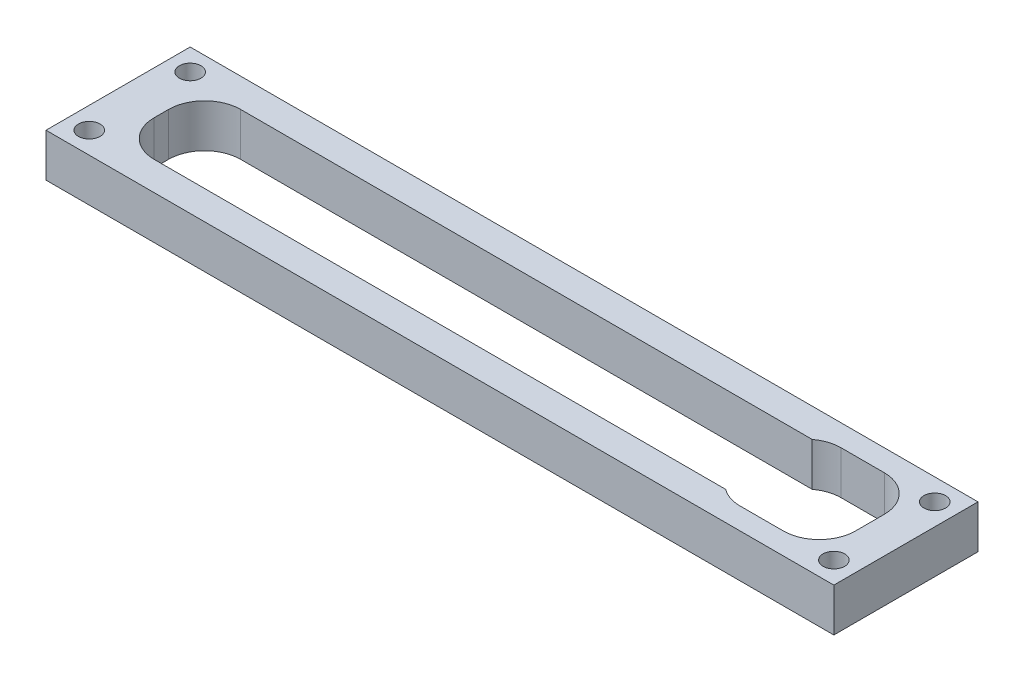
SolidWorks part; units mm, degrees
ref_plane "Front Plane" through (0, 0, 0) normal (0, 0, 1) x (1, 0, 0)
ref_plane "Top Plane" through (0, 0, 0) normal (0, 1, 0) x (1, 0, 0)
ref_plane "Right Plane" through (0, 0, 0) normal (1, 0, 0) x (0, 0, -1)
sketch "Sketch1" plane through (0, 0, 0) normal (0, 1, 0) x (1, 0, 0)
  line L0 (54.6479, 20) -> (54.6479, 0) construction
  line L1 (0, 0) -> (109.2958, 0)
  line L2 (0, 0) -> (0, 20)
  line L3 (0, 20) -> (109.2958, 20)
  line L4 (109.2958, 0) -> (109.2958, 20)
  line L5 (0, 10) -> (109.2958, 10) construction
  line L6 (54.6479, 16) -> (54.6479, 4) construction
  line L7 (6, 16) -> (103.2958, 16)
  line L8 (6, 16) -> (6, 4)
  line L9 (6, 4) -> (103.2958, 4)
  line L10 (103.2958, 16) -> (103.2958, 4)
  line L11 (6, 10) -> (103.2958, 10) construction
  circle A0 centre (3, 17) radius 1.5
  circle A1 centre (3, 3) radius 1.5
  circle A2 centre (106.2958, 3) radius 1.5
  circle A3 centre (106.2958, 17) radius 1.5
  point P17 (54.6479, 10)
  point P18 (54.6479, 10)
  dimension "D7" = 3
  dimension "D1" = 109.2958
  dimension "D2" = 20
  dimension "D3" = 97.2958
  dimension "D4" = 12
  dimension "D5" = 3
  dimension "D6" = 3
extrude "Boss-Extrude1" add sketch "Sketch1" along normal blind 6
sketch "Sketch2" plane through (0, 6, 0) normal (0, 1, 0) x (1, 0, 0)
  line L0 (92, 10) -> (-49908, 10) construction
  line L1 (103.2958, 4) -> (103.2958, 16) construction
  line L2 (90.2958, 17) -> (90.2958, 16)
  line L5 (103.2958, 16) -> (6, 16) construction
  line L6 (97.2958, 17) -> (97.2958, 3) construction
  line L7 (90.2958, 17) -> (104.2958, 17)
  line L9 (90.2958, 3) -> (104.2958, 3)
  line L10 (104.2958, 17) -> (104.2958, 3)
  line L12 (90.2958, 16) -> (103.2958, 16)
  line L13 (103.2958, 16) -> (103.2958, 4)
  line L14 (103.2958, 4) -> (90.2958, 4)
  line L15 (6, 4) -> (103.2958, 4) construction
  line L16 (90.2958, 4) -> (90.2958, 3)
  point P4 (103.2958, 10)
  point P23 (97.2958, 10)
  dimension "D1" = 1
  dimension "D2" = 14
  dimension "D3" = 14
extrude "Cut-Extrude1" cut sketch "Sketch2" against normal through all
fillet "Fillet1" radius 5 6 edges at (104.2958, 3, -17) (104.2958, 3, -3) (90.2958, 3, -17) (90.2958, 3, -3) (6, 3, -4) (6, 3, -16)
equation "\"TrackLength\"= ( ( \"n\" * 28 ) ) / cos ( \"MountAngle\" ) - ( 2 * \"x\" )"
equation "\"D1@Sketch1\"=\"TrackLength\""
equation "\"TrackWidth\"= \"MarbleTrackWidth\" + ( 2 * 4 )"
equation "\"D2@Sketch1\"=\"TrackWidth\""
equation "\"MarbleTrackWidth\"= \"MarbleWidth\" - 1"
equation "\"MarbleTrackLength\"= \"TrackLength\" - ( 2 * 6 )"
equation "\"D3@Sketch1\"=\"MarbleTrackLength\""
equation "\"D4@Sketch1\"=\"MarbleTrackWidth\""
equation "\"MarbleWidth\"= 13"
equation "\"n\"= 4"
equation "\"MountAngle\" = 10"
equation "\"x\"= 14 / cos ( \"MountAngle\" ) - 12"
